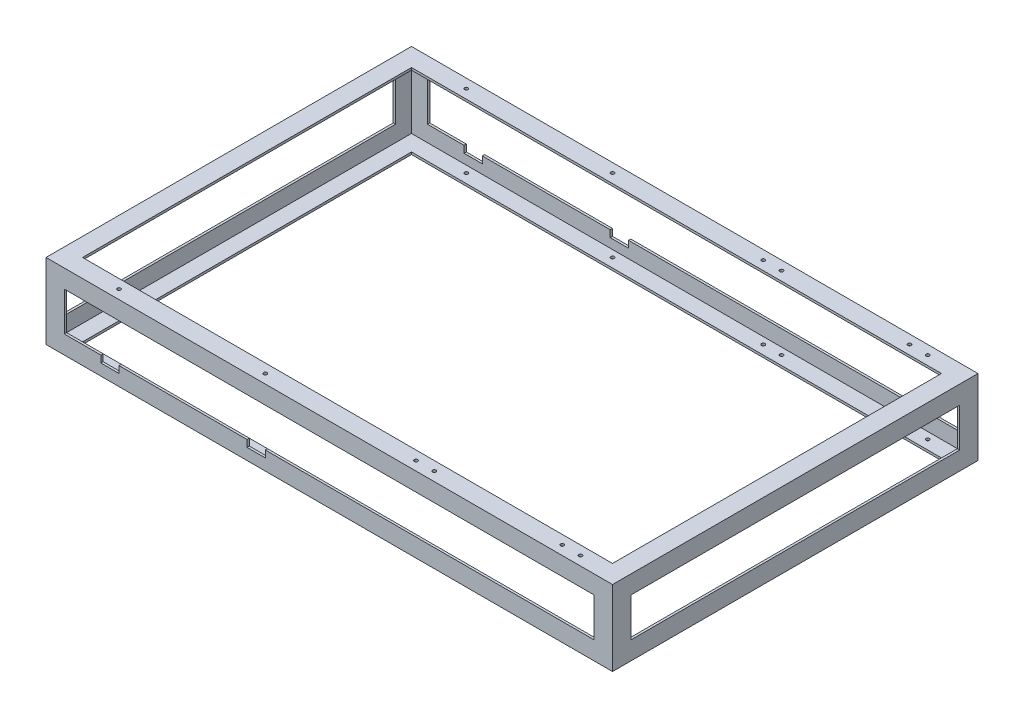
SolidWorks part; units mm, degrees
material "6061 Alloy"
ref_plane "Front Plane" through (0, 0, 0) normal (0, 0, 1) x (1, 0, 0)
ref_plane "Top Plane" through (0, 0, 0) normal (0, 1, 0) x (1, 0, 0)
ref_plane "Right Plane" through (0, 0, 0) normal (1, 0, 0) x (0, 0, -1)
other "Center of Mass"
sketch "Sketch2" plane through (0, 0, 0) normal (1, 0, 0) x (0, 0, -1)
  line L0 (-504.825, -346.075) -> (-504.825, -422.275)
  line L1 (504.825, -422.275) -> (-504.825, -422.275) construction
  line L2 (504.825, -422.275) -> (504.825, 422.275) construction
  line L3 (504.825, 422.275) -> (-504.825, 422.275) construction
  line L4 (-504.825, -422.275) -> (-504.825, 422.275) construction
  line L5 (504.825, -422.275) -> (-504.825, 422.275) construction
  line L6 (504.825, 422.275) -> (-504.825, -422.275) construction
  line L7 (-504.825, -422.275) -> (-428.625, -422.275)
  line L8 (-428.625, -422.275) -> (-428.625, -417.195)
  line L9 (-428.625, -417.195) -> (-498.7519, -417.195)
  line L10 (-498.7519, -417.195) -> (-498.7519, -346.075)
  line L11 (-498.7519, -346.075) -> (-504.825, -346.075)
  line L12 (0, 0) -> (0, -148.4726) construction
  line L13 (0, 0) -> (158.633, 0) construction
  line L14 (498.7519, -417.195) -> (498.7519, -346.075)
  line L15 (428.625, -417.195) -> (498.7519, -417.195)
  line L16 (428.625, -422.275) -> (428.625, -417.195)
  line L17 (504.825, -422.275) -> (428.625, -422.275)
  line L18 (504.825, -346.075) -> (504.825, -422.275)
  line L19 (498.7519, -346.075) -> (504.825, -346.075)
  line L20 (428.625, 417.195) -> (498.7519, 417.195)
  line L21 (428.625, 422.275) -> (428.625, 417.195)
  line L22 (504.825, 422.275) -> (428.625, 422.275)
  line L23 (504.825, 346.075) -> (504.825, 422.275)
  line L24 (498.7519, 346.075) -> (504.825, 346.075)
  line L25 (498.7519, 417.195) -> (498.7519, 346.075)
  line L26 (-498.7519, 417.195) -> (-498.7519, 346.075)
  line L27 (-428.625, 417.195) -> (-498.7519, 417.195)
  line L28 (-428.625, 422.275) -> (-428.625, 417.195)
  line L29 (-504.825, 422.275) -> (-428.625, 422.275)
  line L30 (-504.825, 346.075) -> (-504.825, 422.275)
  line L31 (-498.7519, 346.075) -> (-504.825, 346.075)
  point P0 (0, 0)
  dimension "D1" = 1009.65
  dimension "D2" = 844.55
  dimension "D3" = 76.2
  dimension "D4" = 5.08
extrude "OAL Lenth" [suppressed] add sketch "Sketch2" along normal blind 1574.8
sketch "Sketch3" [suppressed] plane through (0, 0, 0) normal (0, 0, 1) x (1, 0, 0)
  line L0 (0, -422.275) -> (0, -346.075)
  line L1 (1574.8, -346.075) -> (0, -346.075) construction
  line L2 (0, -346.075) -> (0, -422.275) construction
  line L3 (0, -346.075) -> (5.08, -346.075)
  line L4 (5.08, -346.075) -> (5.08, -417.195)
  line L5 (5.08, -417.195) -> (76.2, -417.195)
  line L6 (76.2, -417.195) -> (76.2, -422.275)
  line L7 (1574.8, -422.275) -> (0, -422.275) construction
  line L8 (76.2, -422.275) -> (0, -422.275)
  line L9 (0, 0) -> (697.1877, 0) construction
  line L10 (787.4, 346.075) -> (787.4, -346.075) construction
  line L11 (1574.8, 346.075) -> (0, 346.075) construction
  line L12 (76.2, 422.275) -> (0, 422.275)
  line L13 (76.2, 417.195) -> (76.2, 422.275)
  line L14 (5.08, 417.195) -> (76.2, 417.195)
  line L15 (5.08, 346.075) -> (5.08, 417.195)
  line L16 (0, 346.075) -> (5.08, 346.075)
  line L17 (0, 422.275) -> (0, 346.075)
  line L18 (1574.8, 422.275) -> (1574.8, 346.075)
  line L19 (1574.8, 346.075) -> (1569.72, 346.075)
  line L20 (1569.72, 346.075) -> (1569.72, 417.195)
  line L21 (1569.72, 417.195) -> (1498.6, 417.195)
  line L22 (1498.6, 417.195) -> (1498.6, 422.275)
  line L23 (1498.6, 422.275) -> (1574.8, 422.275)
  line L24 (1498.6, -422.275) -> (1574.8, -422.275)
  line L25 (1498.6, -417.195) -> (1498.6, -422.275)
  line L26 (1569.72, -417.195) -> (1498.6, -417.195)
  line L27 (1569.72, -346.075) -> (1569.72, -417.195)
  line L28 (1574.8, -346.075) -> (1569.72, -346.075)
  line L29 (1574.8, -422.275) -> (1574.8, -346.075)
  dimension "D1" = 5.08
extrude "OAL Width" [suppressed] add sketch "Sketch3" along normal up to surface and the other way up to surface
sketch "Sketch4" [suppressed] plane through (0, 422.275, 0) normal (0, 1, 0) x (1, 0, 0)
  line L0 (0, 504.825) -> (0, 428.625)
  line L1 (0, -428.625) -> (0, -504.825) construction
  line L2 (0, 428.625) -> (5.08, 428.625)
  line L3 (5.08, 428.625) -> (5.08, 499.745)
  line L4 (5.08, 499.745) -> (76.2, 499.745)
  line L5 (76.2, 499.745) -> (76.2, 504.825)
  line L6 (0, 504.825) -> (1574.8, 504.825) construction
  line L7 (76.2, 504.825) -> (0, 504.825)
  line L8 (0, 0) -> (1574.8, 0) construction
  line L9 (1574.8, -428.625) -> (1574.8, -504.825) construction
  line L10 (787.4, 0) -> (787.4, 504.825) construction
  line L11 (76.2, -504.825) -> (0, -504.825)
  line L12 (76.2, -499.745) -> (76.2, -504.825)
  line L13 (5.08, -499.745) -> (76.2, -499.745)
  line L14 (5.08, -428.625) -> (5.08, -499.745)
  line L15 (0, -428.625) -> (5.08, -428.625)
  line L16 (0, -504.825) -> (0, -428.625)
  line L17 (1574.8, -504.825) -> (1574.8, -428.625)
  line L18 (1574.8, -428.625) -> (1569.72, -428.625)
  line L19 (1569.72, -428.625) -> (1569.72, -499.745)
  line L20 (1569.72, -499.745) -> (1498.6, -499.745)
  line L21 (1498.6, -499.745) -> (1498.6, -504.825)
  line L22 (1498.6, -504.825) -> (1574.8, -504.825)
  line L23 (1498.6, 504.825) -> (1574.8, 504.825)
  line L24 (1498.6, 499.745) -> (1498.6, 504.825)
  line L25 (1569.72, 499.745) -> (1498.6, 499.745)
  line L26 (1569.72, 428.625) -> (1569.72, 499.745)
  line L27 (1574.8, 428.625) -> (1569.72, 428.625)
  line L28 (1574.8, 504.825) -> (1574.8, 428.625)
  dimension "D1" = 5.08
  dimension "D2" = 76.2
extrude "OAL Height" [suppressed] add sketch "Sketch4" against normal through all
sketch "Sketch5" plane through (0, 0, 0) normal (1, 0, 0) x (0, 0, -1)
  line L0 (0, 304.8) -> (0, -304.8) construction
  line L1 (-508, -304.8) -> (508, -304.8) construction
  line L2 (-508, -304.8) -> (-508, -254)
  line L3 (-508, -304.8) -> (-457.2, -304.8)
  line L4 (-457.2, -304.8) -> (-457.2, -298.45)
  line L5 (-457.2, -298.45) -> (-501.65, -298.45)
  line L6 (-501.65, -298.45) -> (-501.65, -254)
  line L7 (-501.65, -254) -> (-508, -254)
  line L8 (501.65, -254) -> (508, -254)
  line L9 (501.65, -298.45) -> (501.65, -254)
  line L10 (457.2, -298.45) -> (501.65, -298.45)
  line L11 (457.2, -304.8) -> (457.2, -298.45)
  line L12 (508, -304.8) -> (457.2, -304.8)
  line L13 (508, -304.8) -> (508, -254)
  line L14 (0, -200.025) -> (-176.3903, -200.025) construction
  line L15 (-508, -95.25) -> (508, -95.25) construction
  line L16 (508, -95.25) -> (508, -146.05)
  line L17 (508, -95.25) -> (457.2, -95.25)
  line L18 (457.2, -95.25) -> (457.2, -101.6)
  line L19 (457.2, -101.6) -> (501.65, -101.6)
  line L20 (501.65, -101.6) -> (501.65, -146.05)
  line L21 (501.65, -146.05) -> (508, -146.05)
  line L22 (-501.65, -146.05) -> (-508, -146.05)
  line L23 (-501.65, -101.6) -> (-501.65, -146.05)
  line L24 (-457.2, -101.6) -> (-501.65, -101.6)
  line L25 (-457.2, -95.25) -> (-457.2, -101.6)
  line L26 (-508, -95.25) -> (-457.2, -95.25)
  line L27 (-508, -95.25) -> (-508, -146.05)
  point P4 (0, 0)
  point P8 (0, -304.8)
  point P32 (0, -95.25)
  dimension "D1" = 1016
  dimension "D2" = 609.6
  dimension "D3" = 50.8
  dimension "D4" = 6.35
  dimension "D5" = 104.775
extrude "X Angle Lenth" add sketch "Sketch5" along normal blind 1574.8 separate body
sketch "Sketch6" plane through (0, -304.8, 0) normal (0, -1, 0) x (1, 0, 0)
  line L0 (0, 0) -> (1574.8, 0) construction
  line L1 (1574.8, -508) -> (1574.8, 508) construction
  line L2 (1574.8, -508) -> (1524, -508)
  line L3 (1574.8, -508) -> (1574.8, -457.2)
  line L4 (1574.8, -457.2) -> (1568.45, -457.2)
  line L5 (1568.45, -457.2) -> (1568.45, -501.65)
  line L6 (1568.45, -501.65) -> (1524, -501.65)
  line L7 (1524, -501.65) -> (1524, -508)
  line L8 (1524, 501.65) -> (1524, 508)
  line L9 (1568.45, 501.65) -> (1524, 501.65)
  line L10 (1568.45, 457.2) -> (1568.45, 501.65)
  line L11 (1574.8, 457.2) -> (1568.45, 457.2)
  line L12 (1574.8, 508) -> (1574.8, 457.2)
  line L13 (1574.8, 508) -> (1524, 508)
  line L15 (787.4, 0) -> (787.4, 197.6325) construction
  line L16 (0, -508) -> (0, 508) construction
  line L17 (0, 508) -> (50.8, 508)
  line L18 (0, 508) -> (0, 457.2)
  line L19 (0, 457.2) -> (6.35, 457.2)
  line L20 (6.35, 457.2) -> (6.35, 501.65)
  line L21 (6.35, 501.65) -> (50.8, 501.65)
  line L22 (50.8, 501.65) -> (50.8, 508)
  line L23 (50.8, -501.65) -> (50.8, -508)
  line L24 (6.35, -501.65) -> (50.8, -501.65)
  line L25 (6.35, -457.2) -> (6.35, -501.65)
  line L26 (0, -457.2) -> (6.35, -457.2)
  line L27 (0, -508) -> (0, -457.2)
  line L28 (0, -508) -> (50.8, -508)
  point P3 (787.4, 0)
  point P6 (1574.8, 0)
  point P32 (0, 0)
  dimension "D1" = 50.8
  dimension "D2" = 6.35
  dimension "D3" = 1016
  dimension "D4" = 1574.8
extrude "Y Angle Lenth" add sketch "Sketch6" against normal blind 209.55
sketch "Sketch15" plane through (0, 0, 0) normal (0, 0, 1) x (1, 0, 0)
  line L0 (0, -254) -> (0, -304.8)
  line L1 (0, -95.25) -> (1574.8, -95.25) construction
  line L2 (787.4, -95.25) -> (787.4, 43.9233) construction
  line L3 (1568.45, -254) -> (1574.8, -254)
  line L4 (1568.45, -298.45) -> (1568.45, -254)
  line L5 (1524, -298.45) -> (1568.45, -298.45)
  line L6 (1524, -304.8) -> (1524, -298.45)
  line L7 (0, -304.8) -> (50.8, -304.8)
  line L8 (50.8, -304.8) -> (50.8, -298.45)
  line L9 (50.8, -298.45) -> (6.35, -298.45)
  line L10 (6.35, -298.45) -> (6.35, -254)
  line L11 (6.35, -254) -> (0, -254)
  line L12 (1574.8, -304.8) -> (1524, -304.8)
  line L13 (1574.8, -254) -> (1574.8, -304.8)
  line L20 (787.4, -95.25) -> (787.4, -304.8) construction
  line L21 (1574.8, -304.8) -> (0, -304.8) construction
  line L24 (787.4, -200.025) -> (896.4031, -200.025) construction
  line L27 (1574.8, -146.05) -> (1574.8, -95.25)
  line L28 (1574.8, -95.25) -> (1524, -95.25)
  line L29 (1524, -95.25) -> (1524, -101.6)
  line L30 (1524, -101.6) -> (1568.45, -101.6)
  line L31 (1568.45, -101.6) -> (1568.45, -146.05)
  line L32 (1568.45, -146.05) -> (1574.8, -146.05)
  line L33 (18.8814, -200.025) -> (113.1502, -200.025) construction
  line L35 (6.35, -146.05) -> (0, -146.05)
  line L36 (6.35, -101.6) -> (6.35, -146.05)
  line L37 (50.8, -101.6) -> (6.35, -101.6)
  line L38 (50.8, -95.25) -> (50.8, -101.6)
  line L39 (0, -95.25) -> (50.8, -95.25)
  line L40 (0, -146.05) -> (0, -95.25)
  dimension "D1" = 50.8
  dimension "D2" = 6.35
extrude "Z Angle Lenth" add sketch "Sketch15" against normal up to surface and the other way up to surface up to face at (787.4, -200.025, -508) other way up to face at (787.4, -200.025, 508)
sketch "Sketch16" plane through (0, -95.25, 0) normal (0, 1, 0) x (1, 0, 0)
  line L0 (1409.7, 0) -> (1409.7, 482.6) construction
  line L1 (0, 508) -> (0, -508) construction
  line L2 (1003.3, 0) -> (1003.3, 482.6) construction
  line L3 (584.2, 0) -> (584.2, 482.6) construction
  line L4 (177.8, 0) -> (177.8, 482.6) construction
  line L5 (177.8, 482.6) -> (584.2, 482.6) construction
  line L6 (584.2, 482.6) -> (1003.3, 482.6) construction
  line L7 (1003.3, 482.6) -> (1409.7, 482.6) construction
  line L8 (1409.7, 0) -> (0, 0) construction
  line L9 (1003.3, -482.6) -> (1409.7, -482.6) construction
  line L10 (584.2, -482.6) -> (1003.3, -482.6) construction
  line L11 (177.8, -482.6) -> (584.2, -482.6) construction
  line L12 (0, 508) -> (1574.8, 508) construction
  line L13 (1003.3, 482.6) -> (1054.1, 482.6) construction
  line L14 (1409.7, 482.6) -> (1460.5, 482.6) construction
  line L15 (1003.3, 482.6) -> (1003.3, 498.1872) construction
  line L16 (1003.3, 498.1872) -> (1054.1, 498.1872) construction
  line L17 (1054.1, 498.1872) -> (1054.1, 482.6) construction
  circle A0 centre (1409.7, 482.6) radius 4.7625
  circle A1 centre (1003.3, 482.6) radius 4.7625
  circle A2 centre (584.2, 482.6) radius 4.7625
  circle A3 centre (177.8, 482.6) radius 4.7625
  circle A4 centre (177.8, -482.6) radius 4.7625
  circle A5 centre (584.2, -482.6) radius 4.7625
  circle A6 centre (1003.3, -482.6) radius 4.7625
  circle A7 centre (1409.7, -482.6) radius 4.7625
  circle A8 centre (1054.1, 482.6) radius 4.7625
  circle A9 centre (1460.5, 482.6) radius 4.7625
  circle A10 centre (1460.5, -482.6) radius 4.7625
  circle A11 centre (1054.1, -482.6) radius 4.7625
  dimension "D1" = 9.525
  dimension "D7" = 50.8
  dimension "D2" = 177.8
  dimension "D3" = 406.4
  dimension "D4" = 406.4
  dimension "D5" = 419.1
  dimension "D6" = 25.4
extrude "Wheel Mount LOC Holes" cut sketch "Sketch16" against normal through all
sketch "Sketch17" plane through (0, 0, 508) normal (0, 0, 1) x (1, 0, 0)
  line L0 (1524, -254) -> (50.8, -254) construction
  line L1 (203.2, -273.05) -> (152.4, -273.05)
  line L2 (203.2, -273.05) -> (203.2, -234.95)
  line L3 (203.2, -234.95) -> (152.4, -234.95)
  line L4 (152.4, -273.05) -> (152.4, -234.95)
  line L5 (203.2, -273.05) -> (152.4, -234.95) construction
  line L6 (203.2, -234.95) -> (152.4, -273.05) construction
  line L7 (0, -95.25) -> (0, -304.8) construction
  line L8 (609.6, -273.05) -> (609.6, -234.95)
  line L9 (609.6, -273.05) -> (558.8, -273.05)
  line L10 (558.8, -273.05) -> (558.8, -234.95)
  line L11 (609.6, -234.95) -> (558.8, -234.95)
  point P0 (177.8, -254)
  dimension "D1" = 50.8
  dimension "D2" = 19.05
  dimension "D3" = 177.8
  dimension "D4" = 2
extrude "Front Control Arm Cutouts" cut sketch "Sketch17" against normal through all
sketch "Sketch18" plane through (0, -95.25, 0) normal (0, 1, 0) x (1, 0, 0)
  line L0 (1003.3, -482.6) -> (1030.6685, -482.6) construction
